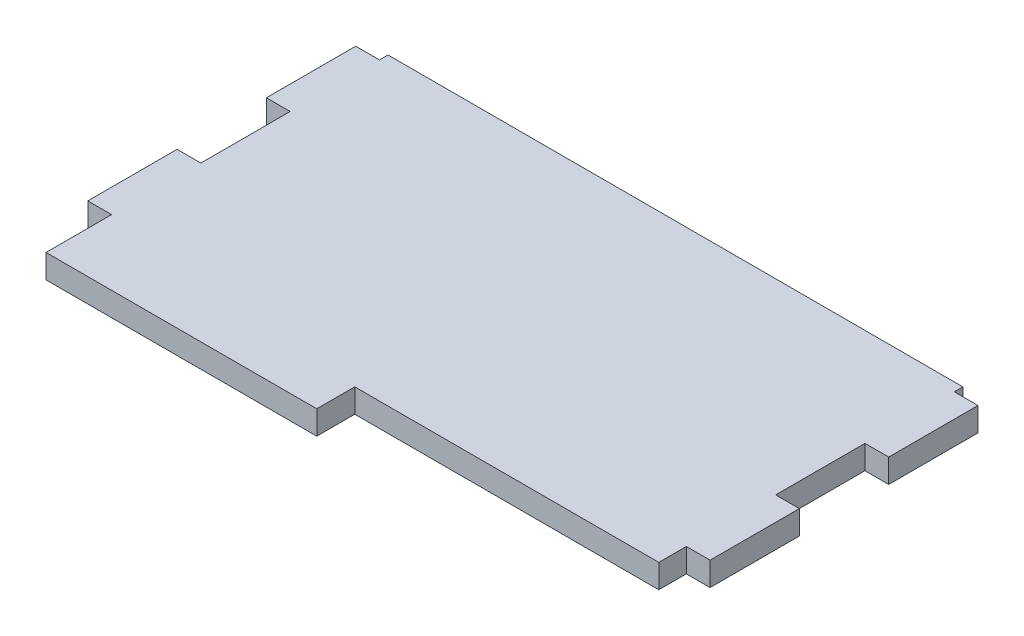
SolidWorks part; units mm, degrees
ref_plane "Front Plane" through (0, 0, 0) normal (0, 0, 1) x (1, 0, 0)
ref_plane "Top Plane" through (0, 0, 0) normal (0, 1, 0) x (1, 0, 0)
ref_plane "Right Plane" through (0, 0, 0) normal (1, 0, 0) x (0, 0, -1)
sketch "Sketch1" plane through (0, 0, 0) normal (0, 1, 0) x (1, 0, 0)
  line L1 (-41.5925, -29.845) -> (41.5925, -29.845)
  line L2 (-41.5925, -29.845) -> (-41.5925, 29.845)
  line L3 (-41.5925, 29.845) -> (41.5925, 29.845)
  line L4 (41.5925, -29.845) -> (41.5925, 29.845)
  line L5 (-41.5925, -29.845) -> (41.5925, 29.845) construction
  line L6 (-41.5925, 29.845) -> (41.5925, -29.845) construction
  point P0 (0, 0)
  dimension "D1" = 83.185
  dimension "D2" = 59.69
extrude "Boss-Extrude1" add sketch "Sketch1" along normal blind 3.175
sketch "Sketch2" plane through (0, 3.175, 0) normal (0, 1, 0) x (1, 0, 0)
  line L1 (-41.5925, 29.845) -> (-24.9555, 29.845)
  line L2 (-41.5925, 29.845) -> (-41.5925, 26.67)
  line L3 (-41.5925, 26.67) -> (-24.9555, 26.67)
  line L4 (-24.9555, 29.845) -> (-24.9555, 26.67)
  line L5 (-41.5925, -29.845) -> (-24.9555, -29.845)
  line L6 (-41.5925, -29.845) -> (-41.5925, -26.67)
  line L7 (-41.5925, -26.67) -> (-24.9555, -26.67)
  line L8 (-24.9555, -29.845) -> (-24.9555, -26.67)
  dimension "D1" = 16.637
  dimension "D2" = 3.175
  dimension "D3" = 3.175
extrude "Cut-Extrude1" cut sketch "Sketch2" against normal blind 3.175
pattern_linear "LPattern1" count 3 spacing 33.274 along (1, 0, 0) of "Cut-Extrude1"
sketch "Sketch3" plane through (0, 3.175, 0) normal (0, 1, 0) x (1, 0, 0)
  line L1 (-41.5925, -29.845) -> (41.5925, -29.845) construction
  line L2 (-41.5925, -29.845) -> (-41.5925, 29.845) construction
  line L3 (-41.5925, 29.845) -> (41.5925, 29.845) construction
  line L4 (41.5925, -29.845) -> (41.5925, 29.845) construction
  line L5 (-41.5925, -29.845) -> (41.5925, 29.845) construction
  line L6 (-41.5925, 29.845) -> (41.5925, -29.845) construction
  line L7 (-41.5925, 29.845) -> (-38.4175, 29.845)
  line L8 (-41.5925, 29.845) -> (-41.5925, 17.907)
  line L9 (-41.5925, 17.907) -> (-38.4175, 17.907)
  line L10 (-38.4175, 29.845) -> (-38.4175, 17.907)
  line L11 (41.5925, 29.845) -> (38.4175, 29.845)
  line L12 (41.5925, 29.845) -> (41.5925, 17.907)
  line L13 (41.5925, 17.907) -> (38.4175, 17.907)
  line L14 (38.4175, 29.845) -> (38.4175, 17.907)
  point P0 (0, 0)
  dimension "D1" = 83.185
  dimension "D2" = 59.69
  dimension "D3" = 3.175
  dimension "D4" = 11.938
  dimension "D5" = 3.175
extrude "Cut-Extrude2" cut sketch "Sketch3" against normal blind 3.175
pattern_linear "LPattern4" count 3 spacing 23.876 along (0, 0, 1) of "Cut-Extrude2"
sketch "Sketch4" plane through (0, 3.175, 0) normal (0, 1, 0) x (1, 0, 0)
  line L0 (-24.9555, 26.67) -> (24.9555, 26.67)
  line L1 (-38.4175, -26.67) -> (38.4175, -26.67) construction
  line L2 (-38.4175, -26.67) -> (-38.4175, 26.67) construction
  line L3 (-38.4175, 26.67) -> (38.4175, 26.67) construction
  line L4 (38.4175, -26.67) -> (38.4175, 26.67) construction
  line L5 (-38.4175, -26.67) -> (38.4175, 26.67) construction
  line L6 (-38.4175, 26.67) -> (38.4175, -26.67) construction
  line L7 (24.9555, 26.67) -> (24.9555, 29.845)
  line L8 (24.9555, 29.845) -> (-24.9555, 29.845)
  line L9 (-24.9555, 29.845) -> (-24.9555, 26.67)
  line L10 (-24.9555, -26.67) -> (-24.9555, -29.845)
  line L11 (-24.9555, -29.845) -> (24.9555, -29.845)
  line L12 (24.9555, -29.845) -> (24.9555, -26.67)
  line L13 (24.9555, -26.67) -> (-24.9555, -26.67)
  line L14 (-38.4175, 26.67) -> (-38.4175, 19.05)
  line L15 (-38.4175, 26.67) -> (38.4175, 26.67)
  line L16 (38.4175, 26.67) -> (38.4175, 19.05)
  line L17 (38.4175, 19.05) -> (-38.4175, 19.05)
  line L18 (38.4175, -26.67) -> (38.4175, -21.59)
  line L19 (38.4175, -21.59) -> (-2.2225, -21.59)
  line L20 (-2.2225, -21.59) -> (-2.2225, -26.67)
  line L21 (-2.2225, -26.67) -> (38.4175, -26.67)
  point P0 (0, 0)
  line M17 (-24.9555, -26.67) -> (-24.9555, -29.845)
  line M18 (-24.9555, -29.845) -> (-8.3185, -29.845)
  line M19 (-8.3185, -29.845) -> (-8.3185, -26.67)
  line M21 (8.3185, -26.67) -> (8.3185, -29.845)
  line M22 (8.3185, -29.845) -> (24.9555, -29.845)
  line M23 (24.9555, -29.845) -> (24.9555, -26.67)
  line M24 (24.9555, -26.67) -> (38.4175, -26.67)
  line M25 (38.4175, -26.67) -> (38.4175, -17.907)
  line M33 (38.4175, 17.907) -> (38.4175, 26.67)
  line M34 (38.4175, 26.67) -> (24.9555, 26.67)
  line M35 (24.9555, 26.67) -> (24.9555, 29.845)
  line M36 (24.9555, 29.845) -> (8.3185, 29.845)
  line M37 (8.3185, 29.845) -> (8.3185, 26.67)
  line M38 (8.3185, 26.67) -> (-8.3185, 26.67)
  line M39 (-8.3185, 26.67) -> (-8.3185, 29.845)
  line M40 (-8.3185, 29.845) -> (-24.9555, 29.845)
  line M41 (-24.9555, 29.845) -> (-24.9555, 26.67)
  line M42 (-24.9555, 26.67) -> (-38.4175, 26.67)
  line M43 (-38.4175, 26.67) -> (-38.4175, 17.907)
  dimension "D1" = 76.835
  dimension "D2" = 53.34
extrude "Cut-Extrude4" cut sketch "Sketch4" against normal blind 3.175 contours L17 L0 M33 M34 M38 M42 M43 | L0 M41 M39 M40 | L0 M37 M35 M36 | L19 L20 L13 M24 M25 | L13 M23 M21 M22 | L13 M19 M17 M18 region at (-16.637, 3.175, -28.2575) region at (0, 3.175, -22.86) region at (16.637, 3.175, -28.2575) region at (-16.637, 3.175, 28.2575) region at (18.0975, 3.175, 24.13) region at (16.637, 3.175, 28.2575)
